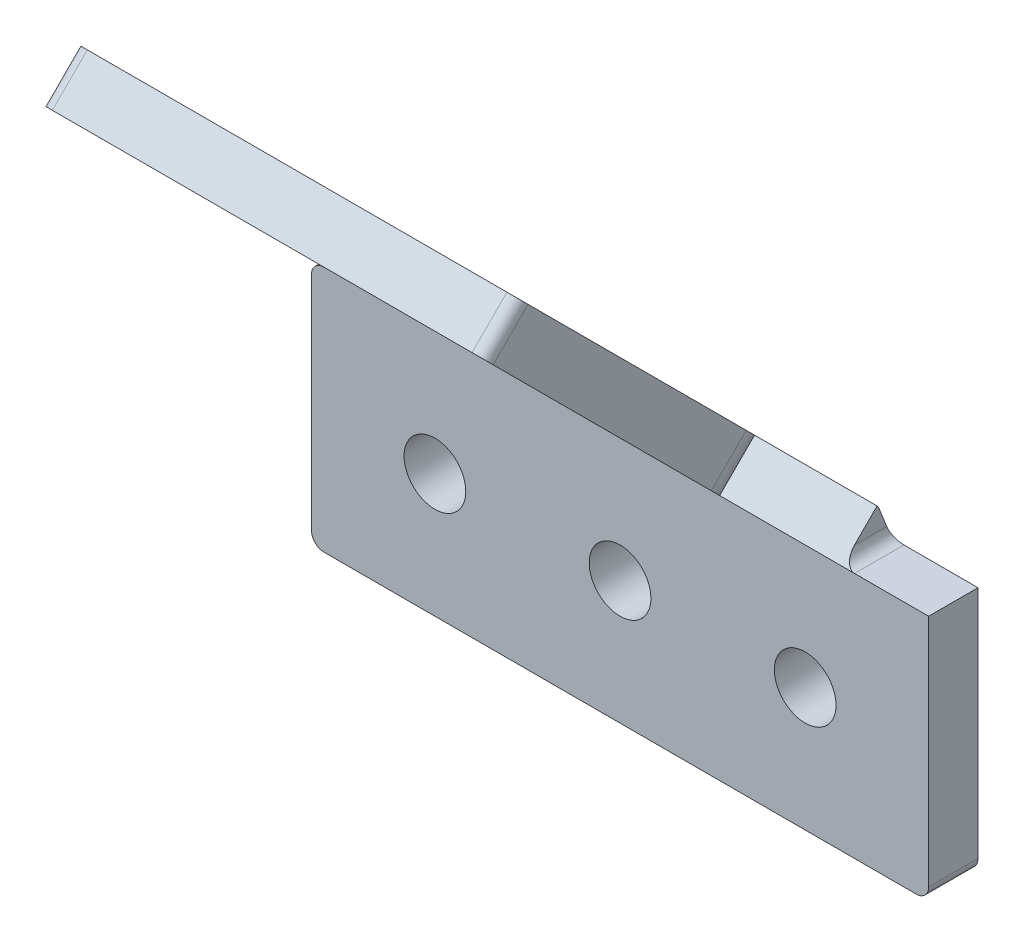
SolidWorks part; units mm, degrees
ref_plane "前视基准面" through (0, 0, 0) normal (0, 0, 1) x (1, 0, 0)
ref_plane "上视基准面" through (0, 0, 0) normal (0, 1, 0) x (1, 0, 0)
ref_plane "右视基准面" through (0, 0, 0) normal (1, 0, 0) x (0, 0, -1)
sketch "草图1" plane through (0, 0, 0) normal (0, 0, 1) x (1, 0, 0)
  line L1 (25, -10) -> (-25, -10)
  line L2 (25, -10) -> (25, 10)
  line L3 (25, 10) -> (-25, 10)
  line L4 (-25, -10) -> (-25, 10)
  line L5 (25, -10) -> (-25, 10) construction
  line L6 (25, 10) -> (-25, -10) construction
  point P0 (0, 0)
  dimension "D1" = 20
  dimension "D2" = 50
extrude "凸台-拉伸1" add sketch "草图1" along normal blind 4
sketch "草图4" plane through (0, 0, 0) normal (1, 0, 0) x (0, 0, -1)
  line L0 (-4, 10) -> (-32.9914, 38.9914)
  line L1 (-32.9914, 38.9914) -> (-30.163, 41.8198)
  line L2 (-30.163, 41.8198) -> (-1.0879, 12.7448)
  line L3 (-1.0879, 12.7448) -> (0, 10)
  line L4 (-4, 10) -> (0, 10)
  line L5 (-4, -10) -> (-4, 10) construction
  line L6 (-4, 10) -> (0, 10) construction
  line L7 (0, -10) -> (0, 10) construction
  dimension "D1" = 135
  dimension "D2" = 41
  dimension "D3" = 4
  dimension "D4" = 45
extrude "凸台-拉伸2" add sketch "草图4" along normal mid plane 36
sketch "草图5" plane through (0, 3, -3) normal (0, -0.7071, 0.7071) x (1, 0, 0)
  line L0 (18, 50.8995) -> (-18, 9.8995) construction
  circle A2 centre (12.7216, 44.888) radius 1.5
  circle A3 centre (-13.6705, 14.8304) radius 1.5
  dimension "D1" = 8
  dimension "D2" = 3
  dimension "D3" = 3
  dimension "D4" = 40
extrude "切除-拉伸1" cut sketch "草图5" against normal through all contours A2 | A2 | A3 | A3 region at (12.7216, 34.7406, 28.7406) region at (-13.6705, 13.4867, 7.4867)
sketch "草图6" plane through (0, 3, -3) normal (0, -0.7071, 0.7071) x (1, 0, 0)
  line L1 (18, 9.8995) -> (3, 9.8995)
  line L2 (18, 9.8995) -> (18, 21.8995)
  line L3 (18, 21.8995) -> (3, 21.8995)
  line L4 (3, 9.8995) -> (3, 21.8995)
  dimension "D1" = 15
  dimension "D2" = 12
extrude "切除-拉伸2" cut sketch "草图6" against normal through all
fillet "圆角1" radius 1 2 edges at (3, 11.4142, 2.5858) (3, 19.8995, 11.0711)
fillet "圆角2" radius 1 7 edges at (25, -10, 2) (-25, -10, 2) (-18, 40.4056, 31.5772) (18, 40.4056, 31.5772) (-25, 10, 2) (-18, 10, 2) (18, 10, 2)
fillet "圆角3" radius 1 1 edges at (0, 12.7448, 1.0879)
sketch "草图7" plane through (0, 3, -3) normal (0, -0.7071, 0.7071) x (1, 0, 0)
  circle A0 centre (12.7216, 44.888) radius 2.5
  circle A1 centre (-13.6705, 14.8304) radius 2.5
  dimension "D1" = 5
  dimension "D2" = 5
extrude "切除-拉伸3" cut sketch "草图7" against normal blind 2
sketch "草图8" plane through (0, 0, 4) normal (0, 0, 1) x (1, 0, 0)
  line L0 (0, -10) -> (0, 0) construction
  line L1 (-24, -10) -> (24, -10) construction
  circle A0 centre (0, 0) radius 2.5
  circle A1 centre (15, 0) radius 2.5
  circle A2 centre (-15, 0) radius 2.5
  dimension "D1" = 5
  dimension "D2" = 10
  dimension "D3" = 2
  dimension "D4" = 2
extrude "切除-拉伸4" cut sketch "草图8" against normal through all
sketch "草图9" plane through (0, 3, -3) normal (0, -0.7071, 0.7071) x (1, 0, 0)
  line L1 (-11, 20.8995) -> (-1, 20.8995)
  line L2 (-11, 20.8995) -> (-11, 16.8995)
  line L3 (-11, 16.8995) -> (-1, 16.8995)
  line L4 (-1, 20.8995) -> (-1, 16.8995)
  line L5 (-0.7, 16.5995) -> (-11.3, 16.5995)
  line L6 (-0.7, 16.5995) -> (-0.7, 21.1995)
  line L7 (-0.7, 21.1995) -> (-11.3, 21.1995)
  line L8 (-11.3, 16.5995) -> (-11.3, 21.1995)
  line L9 (-0.7, 16.5995) -> (-11.3, 21.1995) construction
  line L10 (-0.7, 21.1995) -> (-11.3, 16.5995) construction
  point P6 (-6, 18.8995)
  dimension "D1" = 0.3
  dimension "D2" = 0.3
  dimension "D3" = 0.3
  dimension "D4" = 0.3
extrude "切除-拉伸5" cut sketch "草图9" against normal blind 10 contours L7 L8 L5 L6
fillet "圆角4" radius 3 1 edges at (18, 19.8995, 11.0711)
